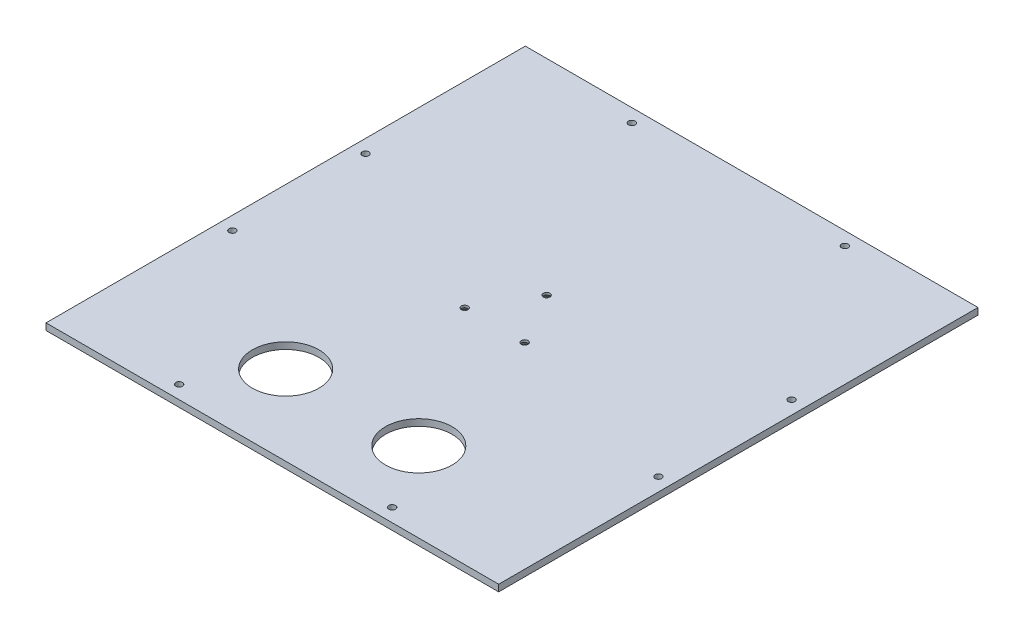
SolidWorks part; units mm, degrees
material "6061-T6 (SS)"
ref_plane "Front Plane" through (0, 0, 0) normal (0, 0, 1) x (1, 0, 0)
ref_plane "Top Plane" through (0, 0, 0) normal (0, 1, 0) x (1, 0, 0)
ref_plane "Right Plane" through (0, 0, 0) normal (1, 0, 0) x (0, 0, -1)
sketch "Sketch1" plane through (0, 0, 0) normal (0, 1, 0) x (1, 0, 0)
  line L1 (0, 0) -> (215.9, 0)
  line L2 (0, 0) -> (0, 228.6)
  line L3 (0, 228.6) -> (215.9, 228.6)
  line L4 (215.9, 0) -> (215.9, 228.6)
  dimension "D1" = 215.9
  dimension "D2" = 228.6
extrude "Boss-Extrude1" add sketch "Sketch1" along normal blind 3.175
sketch "Sketch2" plane through (0, 3.175, 0) normal (0, 1, 0) x (1, 0, 0)
  line L0 (139.7, 38.1) -> (76.2, 38.1) construction
  line L2 (139.7, 38.1) -> (215.9, 38.1) construction
  line L3 (215.9, 0) -> (215.9, 228.6) construction
  line L4 (76.2, 38.1) -> (0, 38.1) construction
  line L5 (0, 0) -> (215.9, 0) construction
  line L6 (0, 228.6) -> (0, 0) construction
  circle A0 centre (139.7, 38.1) radius 15.875
  circle A1 centre (76.2, 38.1) radius 15.875
  point P5 (215.9, 114.3)
  point P13 (107.95, 0)
  point P14 (107.95, 114.3)
  point P15 (-75.9559, 208.7303)
  point P16 (0, 0)
  point P17 (0, 0)
  dimension "D1" = 31.75
  dimension "D2" = 38.1
  dimension "D3" = 63.5
extrude "Cut-Extrude1" cut sketch "Sketch2" against normal through all
sketch "Sketch3" plane through (0, 3.175, 0) normal (0, 1, 0) x (1, 0, 0)
  line L0 (0, 228.6) -> (0, 0) construction
  line L1 (0, 0) -> (215.9, 0) construction
  circle A0 centre (107.95, 130.81) radius 1.5875
  circle A1 centre (122.2481, 106.045) radius 1.5875
  circle A2 centre (93.6519, 106.045) radius 1.5875
  point P0 (0, 114.3)
  point P1 (107.95, 0)
  point P4 (107.95, 114.3)
  dimension "D2" = 3.175
  dimension "D1" = 16.51
  dimension "D3" = 3
extrude "Cut-Extrude2" cut sketch "Sketch3" against normal through all
sketch "Sketch4" plane through (0, 3.175, 0) normal (0, 1, 0) x (1, 0, 0)
  line L0 (215.9, 228.6) -> (0, 228.6) construction
  line L1 (0, 228.6) -> (0, 0) construction
  line L2 (0, 0) -> (215.9, 0) construction
  line L3 (107.95, 228.6) -> (107.95, 0) construction
  circle A0 centre (6.35, 146.05) radius 1.5875
  circle A1 centre (6.35, 82.55) radius 1.5875
  circle A2 centre (57.15, 6.35) radius 1.5875
  circle A3 centre (57.15, 222.25) radius 1.5875
  circle A4 centre (158.75, 6.35) radius 1.5875
  circle A5 centre (209.55, 82.55) radius 1.5875
  circle A6 centre (209.55, 146.05) radius 1.5875
  circle A7 centre (158.75, 222.25) radius 1.5875
  point P14 (107.95, 0)
  point P15 (107.95, 228.6)
  dimension "D1" = 3.175
  dimension "D2" = 6.35
  dimension "D3" = 6.35
  dimension "D4" = 6.35
  dimension "D5" = 6.35
  dimension "D6" = 57.15
  dimension "D7" = 57.15
  dimension "D8" = 82.55
  dimension "D9" = 82.55
extrude "Cut-Extrude3" cut sketch "Sketch4" against normal through all
chamfer "Chamfer1" distance 2.1082 angle 41 3 edges at (93.6519, 0, -104.4575) (122.2481, 0, -104.4575) (107.95, 0, -129.2225) first distance on face at (93.6519, 0, -104.4575) first distance on face at (122.2481, 0, -104.4575) first distance on face at (107.95, 0, -129.2225)
